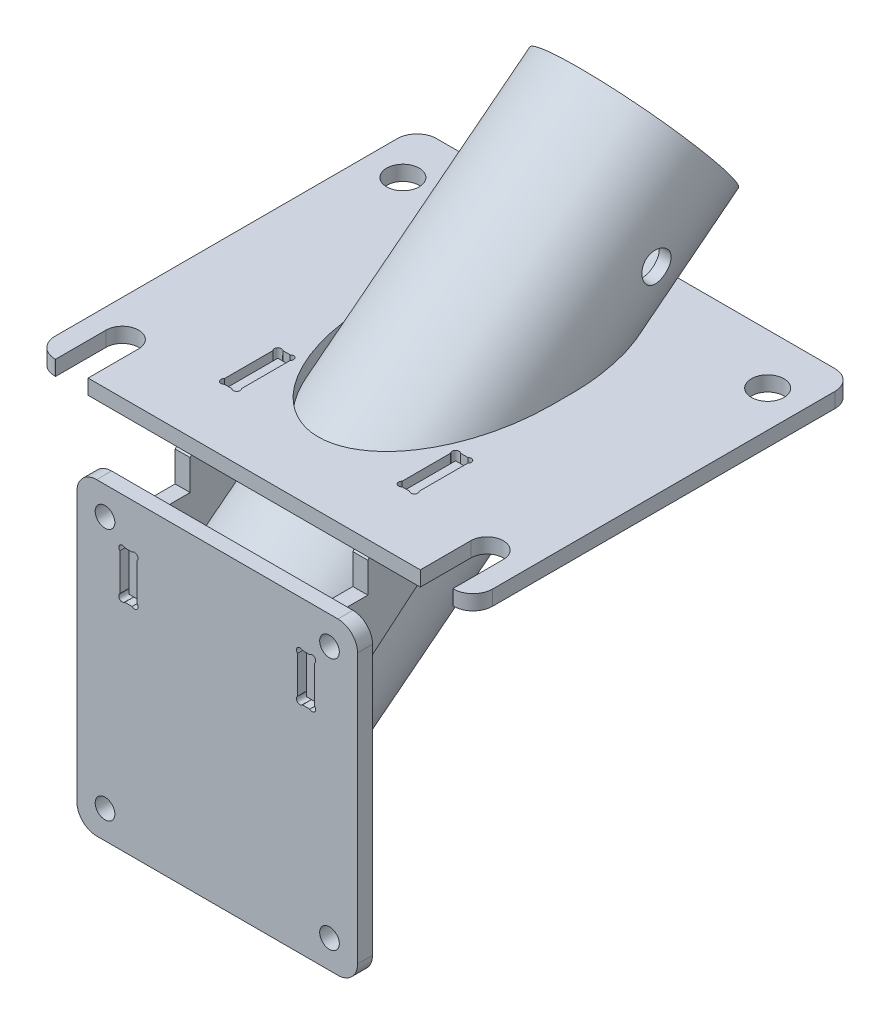
SolidWorks part; units mm, degrees
material "AISI 304 Stainless Steel"
ref_plane "Front Plane" through (0, 0, 0) normal (0, 0, 1) x (1, 0, 0)
ref_plane "Top Plane" through (0, 0, 0) normal (0, 1, 0) x (1, 0, 0)
ref_plane "Right Plane" through (0, 0, 0) normal (1, 0, 0) x (0, 0, -1)
ref_axis "Axis1" through (0, 0, -88.99) along (0, 0, 1)
ref_axis "Axis2" through (0, -55, 0) along (0, 1, 0)
ref_axis "Axis3" through (-88.99, 0, 0) along (1, 0, 0)
sketch "Sketch1" plane through (0, 0, 0) normal (0, 1, 0) x (1, 0, 0)
  line L1 (33, -35) -> (-33, -35)
  line L2 (38, -30) -> (38, 30)
  line L3 (33, 35) -> (-33, 35)
  line L4 (-38, -30) -> (-38, 30)
  line L5 (38, -35) -> (-38, 35) construction
  line L6 (38, 35) -> (-38, -35) construction
  arc A0 (38, 30) -> (33, 35) centre (33, 30) ccw
  arc A1 (33, -35) -> (38, -30) centre (33, -30) ccw
  arc A2 (-33, -35) -> (-38, -30) centre (-33, -30) cw
  arc A3 (-33, 35) -> (-38, 30) centre (-33, 30) ccw
  point P0 (0, 0)
  dimension "D1" = 5
  dimension "D2" = 76
  dimension "D3" = 70
extrude "Boss-Extrude1" [suppressed] add sketch "Sketch1" along normal blind 2.3813
sketch "Sketch3" [suppressed] plane through (0, 0, 0) normal (0, 0, 1) x (1, 0, 0)
  line L0 (-32.6449, 0.7663) -> (82.2618, 97.1844)
  line L1 (82.2618, 97.1844) -> (80.9067, 98.7994)
  line L2 (80.9067, 98.7994) -> (-34, 2.3813)
  line L3 (-34, 2.3813) -> (-32.6449, 0.7663)
  line L4 (-9.3029, 2.3813) -> (47.0344, 49.6539) construction
  line L5 (-33, 2.3813) -> (33, 2.3813) construction
  line L6 (-33, 2.3813) -> (-38, 2.3813) construction
  line L7 (-34, 2.3813) -> (-38, 2.3813) construction
  line L8 (82.2618, 97.1844) -> (82.2618, 2.3813) construction
  dimension "D1" = 40
  dimension "D2" = 2.1082
  dimension "D3" = 150
  dimension "D4" = 4
  dimension "D5" = 31.75
revolve "Revolve1" [suppressed] add sketch "Sketch3" angle 360 about L4
sketch "Sketch4" [suppressed] plane through (0, 0, 35) normal (0, 0, 1) x (1, 0, 0)
  line L2 (-13.5915, -21.9407) -> (12.5564, 0)
  line L4 (-32.0019, 0) -> (-13.5915, -21.9407) construction
  line L5 (-33, 0) -> (33, 0) construction
  line L6 (-13.5915, -21.9407) -> (-32.0019, 0)
  line L7 (-32.0019, 0) -> (12.5564, 0)
  line M3 (-33, 0) -> (33, 0)
extrude "Cut-Extrude1" [suppressed] cut sketch "Sketch4" against normal through all contours L6 L2 M3
sketch "Sketch5" plane through (0, 0, 0) normal (1, 0, 0) x (0, 0, -1)
  line L0 (0, 0) -> (0, 69)
  line L1 (0, 69) -> (78.5, 69)
  line L2 (0, 34.5) -> (44.158, 69) construction
  line L3 (-21.1233, 38.1424) -> (18.3727, 69)
  line L4 (0, 14.3543) -> (69.9433, 69)
  line L5 (18.3727, 69) -> (63.1939, 104.0181)
  line L6 (63.1939, 104.0181) -> (64.4918, 102.3568)
  line L7 (64.4918, 102.3568) -> (-19.8253, 36.4811)
  line L8 (-21.1233, 38.1424) -> (-1.576, 13.123)
  line L9 (-1.576, 13.123) -> (0, 14.3543)
  dimension "D1" = 38
  dimension "D2" = 31.75
  dimension "D3" = 78.5
  dimension "D4" = 69
  dimension "D5" = 2.1082
  dimension "D6" = 2
  dimension "D7" = 107
revolve "Revolve2" add sketch "Sketch5" angle 360 about L2 region at (0, 45.3213, 10.2406) region at (0, 61.135, -10.0668) region at (0, 86.0971, -41.9543)
sketch "Sketch6" plane through (0, 0, 0) normal (1, 0, 0) x (0, 0, -1)
  line L0 (0, 0) -> (0, 69) construction
  line L1 (1.3335, 7) -> (-1.3335, 7)
  line L2 (1.3335, 7) -> (1.3335, 62)
  line L3 (1.3335, 62) -> (-1.3335, 62)
  line L4 (-1.3335, 7) -> (-1.3335, 62)
  line L5 (1.3335, 7) -> (-1.3335, 62) construction
  line L6 (1.3335, 62) -> (-1.3335, 7) construction
  point P0 (0, 34.5)
  dimension "D1" = 2.667
  dimension "D2" = 55
extrude "Boss-Extrude2" add sketch "Sketch6" along normal mid plane 50 separate body
sketch "Sketch7" plane through (0, 0, 0) normal (1, 0, 0) x (0, 0, -1)
  line L0 (0, 69) -> (78.5, 69) construction
  line L1 (73.25, 67.6665) -> (5.25, 67.6665)
  line L2 (73.25, 67.6665) -> (73.25, 70.3335)
  line L3 (73.25, 70.3335) -> (5.25, 70.3335)
  line L4 (5.25, 67.6665) -> (5.25, 70.3335)
  line L5 (73.25, 67.6665) -> (5.25, 70.3335) construction
  line L6 (73.25, 70.3335) -> (5.25, 67.6665) construction
  point P0 (39.25, 69)
  dimension "D1" = 2.667
  dimension "D2" = 68
extrude "Boss-Extrude3" add sketch "Sketch7" along normal mid plane 78 separate body contours L3 L4 L1 L2
sketch "Sketch8" plane through (0, 0, 0) normal (1, 0, 0) x (0, 0, -1)
  line L0 (1.3335, 57.0599) -> (11.9401, 67.6665)
  line L1 (1.3335, 7) -> (1.3335, 62) construction
  line L2 (73.25, 67.6665) -> (5.25, 67.6665) construction
  line L3 (11.9401, 67.6665) -> (31.3258, 67.6665)
  line L5 (31.3258, 67.6665) -> (1.3335, 42.5)
  line L6 (1.3335, 42.5) -> (1.3335, 57.0599)
  line L8 (0, 69) -> (78.5, 69) construction
  dimension "D1" = 45
  dimension "D2" = 40
  dimension "D3" = 26.5
  dimension "D4" = 15
extrude "Boss-Extrude4" add sketch "Sketch8" along normal blind 2.667 from offset 14.5 separate body
hole_wizard "M5x0.8 Tapped Hole1" positions "Sketch10" profile "Sketch9" tap size "M5x0.8" standard "ANSI Metric" end condition through all
sketch "Sketch10" plane through (0, 0, 1.3335) normal (0, 0, 1) x (1, 0, 0)
  line L0 (0, 7) -> (0, 34.5) construction
  line L1 (25, 7) -> (-25, 7) construction
  line L2 (0, 34.5) -> (-25, 34.5) construction
  line L3 (-25, 62) -> (-25, 7) construction
  point P0 (-20, 57)
  point P14 (-20, 12)
  point P15 (20, 12)
  point P16 (20, 57)
  dimension "D1" = 40
  dimension "D2" = 45
sketch "Sketch9" plane through (-20, 57, 1.3335) normal (1, 0, 0) x (0, -1, 0)
  line L0 (0, 0) -> (0, 84.0746)
  line L1 (0, 84.0746) -> (1.75, 84.0746)
  line L2 (1.75, 84.0746) -> (1.75, 0)
  line L5 (1.75, 0) -> (0, 0)
  line L11 (0, -6.35) -> (0, 107.95) construction
  dimension "Thread Major Dia." = 3.5
  dimension "Thru Tap Drill Depth" = 84.0746
hole_wizard "M5 Clearance Hole1" positions "Sketch12" profile "Sketch11" hole size "M5" standard "ANSI Metric" end condition through all
sketch "Sketch12" plane through (0, 70.3335, 0) normal (0, 1, 0) x (1, 0, 0)
  line L0 (0, 5.25) -> (0, 39.25) construction
  line L1 (39, 5.25) -> (-39, 5.25) construction
  line L2 (0, 39.25) -> (-39, 39.25) construction
  line L3 (-39, 73.25) -> (-39, 5.25) construction
  point P0 (-32.5, 64.25)
  point P14 (-32.5, 14.25)
  point P15 (32.5, 14.25)
  point P16 (32.5, 64.25)
  dimension "D1" = 50
  dimension "D2" = 65
sketch "Sketch11" plane through (-32.5, 70.3335, -64.25) normal (1, 0, 0) x (0, 0, 1)
  line L0 (0, 0) -> (0, 63.3335)
  line L1 (0, 63.3335) -> (2.9, 63.3335)
  line L2 (2.9, 63.3335) -> (2.9, 0)
  line L5 (2.9, 0) -> (0, 0)
  line L11 (0, -6.35) -> (0, 107.95) construction
  dimension "Thru Hole Dia." = 5.8
  dimension "Thru Hole Depth" = 63.3335
fillet "Fillet1" radius 3.5 4 edges at (39, 69, -73.25) (39, 69, -5.25) (-39, 69, -5.25) (-39, 69, -73.25)
sketch "Sketch14" plane through (0, 70.3335, 0) normal (0, 1, 0) x (1, 0, 0)
  line L0 (0, 0) -> (0, 5.25) construction
  line L1 (35.5, 5.25) -> (-35.5, 5.25) construction
  line L2 (-32.5, -3.75) -> (-32.5, 14.25) construction
  line L3 (-35.4, -3.75) -> (-35.4, 14.25)
  line L4 (-29.6, -3.75) -> (-29.6, 14.25)
  line L5 (32.5, -3.75) -> (32.5, 14.25) construction
  line L6 (35.4, -3.75) -> (35.4, 14.25)
  line L7 (29.6, -3.75) -> (29.6, 14.25)
  arc A0 (-35.4, -3.75) -> (-29.6, -3.75) centre (-32.5, -3.75) ccw
  arc A1 (-29.6, 14.25) -> (-35.4, 14.25) centre (-32.5, 14.25) ccw
  circle A2 centre (-32.5, 14.25) radius 2.9 construction
  arc A3 (35.4, -3.75) -> (29.6, -3.75) centre (32.5, -3.75) cw
  arc A4 (29.6, 14.25) -> (35.4, 14.25) centre (32.5, 14.25) cw
  point P8 (-32.5, 5.25)
  point P17 (32.5, 5.25)
extrude "Cut-Extrude2" cut sketch "Sketch14" against normal through all
fillet "Fillet2" radius 3.5 4 edges at (-25, 62, 0) (-25, 7, 0) (25, 7, 0) (25, 62, 0)
sketch "Sketch18" plane through (0, 0, -1.3335) normal (0, 0, -1) x (-1, 0, 0)
  ellipse E0 centre (0, 35.5418) end of major axis (0, 15.3962) minor radius 15.875
  ellipse E1 centre (0, 35.5418) end of major axis (0, 15.3962) minor radius 15.875
sketch "Sketch16" plane through (0, 0, 1.3335) normal (0, 0, 1) x (1, 0, 0)
  ellipse E0 centre (0, 33.4582) end of major axis (0, 13.3125) minor radius 15.875
  ellipse E1 centre (0, 33.4582) end of major axis (0, 13.3125) minor radius 15.875 construction
  ellipse E2 centre (0, 35.5418) end of major axis (0, 15.3962) minor radius 15.875 construction
  ellipse E3 centre (0, 35.5418) end of major axis (0, 15.3962) minor radius 15.875
  point P11 (0, 12.5625)
  dimension "D1" = 0.75
extrude "Cut-Extrude3" [suppressed] cut sketch "Sketch16" against normal through all
sketch "Sketch17" plane through (-25, 0, 0) normal (-1, 0, 0) x (0, 0, 1)
  line L0 (1.3335, 53.6038) -> (21.1233, 38.1424)
  line L1 (21.1233, 38.1424) -> (1.3335, 12.8126)
  line L4 (-1.3335, 58.5) -> (-1.3335, 10.5)
  line L5 (-1.3335, 10.5) -> (1.3335, 10.5)
  line L6 (1.3335, 10.5) -> (1.3335, 58.5)
  line L7 (1.3335, 58.5) -> (-1.3335, 58.5)
  line L8 (-1.3335, 58.5) -> (-1.3335, 10.5)
  line L9 (-1.3335, 10.5) -> (1.3335, 10.5)
  line L10 (1.3335, 10.5) -> (1.3335, 58.5)
  line L11 (1.3335, 58.5) -> (-1.3335, 58.5)
  line L12 (1.576, 13.123) -> (21.1233, 38.1424) construction
  line L13 (21.1233, 38.1424) -> (-63.1939, 104.0181) construction
  line M7 (1.3335, 10.5) -> (1.3335, 58.5)
  dimension "D1" = 0
extrude "Cut-Extrude4" cut sketch "Sketch17" against normal through all contours L1 L0 M7 region at (-25, 34.8529, 7.9301)
sketch "Sketch19" plane through (0, 67.6665, 0) normal (0, -1, 0) x (1, 0, 0)
  ellipse E0 centre (0, -42.4512) end of major axis (0, -68.2365) minor radius 15.875
  ellipse E1 centre (0, -42.4512) end of major axis (0, -68.2365) minor radius 15.875
sketch "Sketch20" plane through (0, 70.3335, 0) normal (0, 1, 0) x (1, 0, 0)
  line L0 (-15.875, 45.8648) -> (-15.875, 42.4512)
  line L1 (15.875, 42.4512) -> (15.875, 45.8648)
  ellipse E0 centre (0, 45.8648) end of major axis (0, 71.6501) minor radius 15.875
  ellipse E1 centre (0, 45.8648) end of major axis (0, 71.6501) minor radius 15.875 (-15.8402, 44.158) -> (15.8402, 44.158) ccw
  ellipse E2 centre (0, 42.4512) end of major axis (0, 68.2365) minor radius 15.875 construction
  ellipse E3 centre (0, 42.4512) end of major axis (0, 68.2365) minor radius 15.875 (-15.875, 42.4512) -> (15.875, 42.4512) ccw
  ellipse E4 centre (0, 45.8648) end of major axis (0, 71.6501) minor radius 15.875 (15.875, 45.8648) -> (-15.875, 45.8648) ccw
  ellipse E5 centre (0, 42.4512) end of major axis (0, 68.2365) minor radius 15.875 (15.8402, 44.158) -> (-15.8402, 44.158) ccw
extrude "Cut-Extrude6" cut sketch "Sketch20" against normal blind 6.35 contours L1 E4 L0 E3 E5 E1 | E1 E5 region at (0.0001, 70.3335, -19.6482) region at (-12.0313, 70.3335, -61.7632) region at (0, 70.3335, -44.1564)
sketch "Sketch21" plane through (17.167, 0, 0) normal (1, 0, 0) x (0, 0, -1)
  line L0 (1.3335, 53.7799) -> (0.0835, 53.7799)
  line L1 (1.3335, 10.5) -> (1.3335, 58.5) construction
  line L2 (0.0835, 53.7799) -> (0.0835, 45.7799)
  line L3 (0.0835, 45.7799) -> (1.3335, 45.7799)
  line L4 (0.0835, 49.7799) -> (1.3335, 49.7799) construction
  line L5 (1.3335, 57.0599) -> (1.3335, 42.5) construction
  line L6 (1.3335, 53.7799) -> (1.3335, 45.7799)
  line L7 (21.6329, 67.6665) -> (21.6329, 68.9165) construction
  line L8 (31.3258, 67.6665) -> (11.9401, 67.6665) construction
  line L10 (16.6329, 67.6665) -> (26.6329, 67.6665)
  line L11 (16.6329, 67.6665) -> (16.6329, 68.9165)
  line L12 (16.6329, 68.9165) -> (26.6329, 68.9165)
  line L13 (26.6329, 67.6665) -> (26.6329, 68.9165)
  dimension "D1" = 8
  dimension "D2" = 1.25
  dimension "D3" = 10
  dimension "D4" = 1.25
extrude "Boss-Extrude5" add sketch "Sketch21" against normal up to surface (2.667 mm away) up to face at (14.5, 58.7232, -11.4832)
sketch "Sketch22" plane through (0, 70.3335, 0) normal (0, 1, 0) x (1, 0, 0)
  line L0 (14.5, 26.6329) -> (17.167, 26.6329) construction
  line L1 (14.3, 16.4329) -> (17.367, 16.4329)
  line L2 (14.3, 16.4329) -> (14.3, 26.8329)
  line L3 (14.3, 26.8329) -> (17.367, 26.8329)
  line L4 (17.367, 16.4329) -> (17.367, 26.8329)
  line L5 (14.3, 16.4329) -> (17.367, 26.8329) construction
  line L6 (14.3, 26.8329) -> (17.367, 16.4329) construction
  line L7 (17.167, 26.6329) -> (17.167, 16.6329) construction
  line L8 (15.8335, 16.6329) -> (15.8335, 26.6329) construction
  line L9 (14.5, 16.6329) -> (17.167, 16.6329) construction
  line L10 (0, 0) -> (0, 63.1939) construction
  line L11 (-14.3, 16.4329) -> (-14.3, 26.8329)
  line L12 (-14.3, 16.4329) -> (-17.367, 16.4329)
  line L13 (-17.367, 16.4329) -> (-17.367, 26.8329)
  line L14 (-14.3, 26.8329) -> (-17.367, 26.8329)
  ellipse E0 centre (0, 72.9675) end of major axis (-15.875, 72.9675) minor radius 9.7736 construction
  point P0 (15.8335, 21.6329)
  dimension "D1" = 0.2
  dimension "D2" = 0.2
extrude "Cut-Extrude7" cut sketch "Sketch22" against normal through all
sketch "Sketch23" plane through (0, 0, 1.3335) normal (0, 0, 1) x (1, 0, 0)
  line L0 (15.8335, 45.7799) -> (15.8335, 53.7799) construction
  line L1 (14.3, 45.5799) -> (17.367, 45.5799)
  line L2 (14.3, 45.5799) -> (14.3, 53.9799)
  line L3 (14.3, 53.9799) -> (17.367, 53.9799)
  line L4 (17.367, 45.5799) -> (17.367, 53.9799)
  line L5 (14.3, 45.5799) -> (17.367, 53.9799) construction
  line L6 (14.3, 53.9799) -> (17.367, 45.5799) construction
  line L7 (14.5, 45.7799) -> (17.167, 45.7799) construction
  line L8 (14.5, 53.7799) -> (17.167, 53.7799) construction
  line L9 (14.5, 53.7799) -> (17.167, 53.7799) construction
  line L10 (17.167, 53.7799) -> (17.167, 45.7799) construction
  line L11 (0, 0) -> (0, 73.457) construction
  line L12 (-14.3, 45.5799) -> (-17.367, 45.5799)
  line L13 (-14.3, 45.5799) -> (-14.3, 53.9799)
  line L14 (-14.3, 53.9799) -> (-17.367, 53.9799)
  line L15 (-17.367, 45.5799) -> (-17.367, 53.9799)
  point P0 (15.8335, 49.7799)
  dimension "D1" = 0.2
  dimension "D2" = 0.2
extrude "Cut-Extrude8" cut sketch "Sketch23" against normal through all
sketch "Sketch24" plane through (17.167, 0, 0) normal (1, 0, 0) x (0, 0, -1)
  line L0 (8.3335, 64.0599) -> (8.3335, 58.6665)
  line L1 (11.9401, 67.6665) -> (1.3335, 57.0599) construction
  line L2 (8.3335, 58.6665) -> (2.9401, 58.6665)
  line L3 (2.9401, 58.6665) -> (8.3335, 64.0599)
  line L4 (1.3335, 10.5) -> (1.3335, 58.5) construction
  line L5 (69.75, 67.6665) -> (8.75, 67.6665) construction
  dimension "D1" = 7
  dimension "D2" = 9
extrude "Cut-Extrude9" cut sketch "Sketch24" against normal through all
mirror "Mirror1" about plane through (0, 0, 0) normal (1, 0, 0) of bodies 118 107
sketch "Sketch25" plane through (39, 0, 0) normal (1, 0, 0) x (0, 0, -1)
  line L0 (72.9675, 91.5085) -> (61.1473, 82.2735) construction
  line L3 (81.4432, 80.6601) -> (64.4918, 102.3568) construction
  line L4 (82.7411, 78.9988) -> (63.1939, 104.0181) construction
  circle A0 centre (61.1473, 82.2735) radius 2.6
  dimension "D1" = 5.2
  dimension "D2" = 15
extrude "Cut-Extrude10" cut sketch "Sketch25" against normal through all
sketch "Sketch26" plane through (0, 70.3335, 0) normal (0, 1, 0) x (1, 0, 0)
  line L0 (14.3, 26.8329) -> (14.7419, 26.391) construction
  line L1 (17.367, 26.8329) -> (14.3, 26.8329) construction
  line L2 (15.8335, 26.8329) -> (15.8335, 21.6329) construction
  line L3 (15.8335, 21.6329) -> (14.3, 21.6329) construction
  line L4 (14.3, 26.8329) -> (14.3, 16.4329) construction
  line L5 (0, 0) -> (0, 58.9829) construction
  circle A0 centre (14.7419, 26.391) radius 0.625
  circle A1 centre (16.9251, 26.391) radius 0.625
  circle A2 centre (16.9251, 16.8749) radius 0.625
  circle A3 centre (14.7419, 16.8749) radius 0.625
  circle A4 centre (-16.9251, 26.391) radius 0.625
  circle A5 centre (-14.7419, 26.391) radius 0.625
  circle A6 centre (-16.9251, 16.8749) radius 0.625
  circle A7 centre (-14.7419, 16.8749) radius 0.625
  dimension "D1" = 1.25
  dimension "D2" = 45
extrude "Cut-Extrude11" cut sketch "Sketch26" against normal through all
sketch "Sketch27" plane through (0, 0, 1.3335) normal (0, 0, 1) x (1, 0, 0)
  line L0 (15.8335, 53.9799) -> (15.8335, 49.7799) construction
  line L1 (17.367, 53.9799) -> (14.3, 53.9799) construction
  line L2 (15.8335, 49.7799) -> (14.3, 49.7799) construction
  line L3 (14.3, 53.9799) -> (14.3, 45.5799) construction
  line L4 (14.7419, 53.538) -> (14.3, 53.9799) construction
  line L5 (0, 7) -> (0, 62) construction
  line L6 (21.5, 7) -> (-21.5, 7) construction
  line L7 (21.5, 62) -> (-21.5, 62) construction
  circle A0 centre (14.7419, 53.538) radius 0.625
  circle A1 centre (16.9251, 53.538) radius 0.625
  circle A2 centre (16.9251, 46.0219) radius 0.625
  circle A3 centre (14.7419, 46.0219) radius 0.625
  circle A4 centre (-16.9251, 53.538) radius 0.625
  circle A5 centre (-14.7419, 53.538) radius 0.625
  circle A6 centre (-16.9251, 46.0219) radius 0.625
  circle A7 centre (-14.7419, 46.0219) radius 0.625
  dimension "D2" = 1.25
  dimension "D1" = 45
extrude "Cut-Extrude12" cut sketch "Sketch27" against normal through all
sketch "Sketch28" plane through (0, 0, 0) normal (1, 0, 0) x (0, 0, -1)
  line L2 (-1.3753, 53.5712) -> (1.3335, 55.6875)
  line L3 (-21.1233, 38.1424) -> (18.3727, 69) construction
  line L4 (1.3335, 55.6875) -> (1.3335, 15.3962)
  line L7 (0, 34.5) -> (72.9675, 91.5085) construction
  line L8 (81.4432, 80.6601) -> (64.4918, 102.3568) construction
  line L9 (0, 14.3543) -> (69.9433, 69) construction
  line L10 (1.3335, 10.5) -> (1.3335, 58.5) construction
  line L11 (1.3335, 15.3962) -> (-1.3335, 13.3125)
  line L12 (-1.3335, 13.3125) -> (-1.3753, 53.5712)
extrude "Cut-Extrude14" cut sketch "Sketch28" against normal through all both and the other way through all
